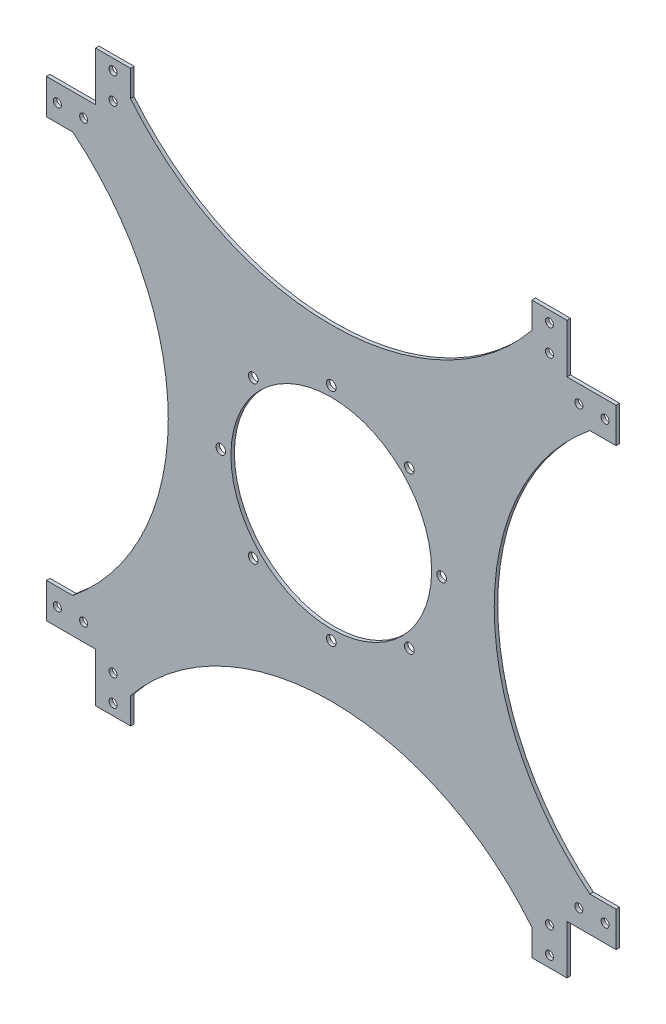
SolidWorks part; units mm, degrees
ref_plane "Front Plane" through (0, 0, 0) normal (0, 0, 1) x (1, 0, 0)
ref_plane "Top Plane" through (0, 0, 0) normal (0, 1, 0) x (1, 0, 0)
ref_plane "Right Plane" through (0, 0, 0) normal (1, 0, 0) x (0, 0, -1)
sketch "Sketch1" plane through (0, 0, 0) normal (0, 0, 1) x (1, 0, 0)
  line L0 (0, 0) -> (367.2182, 0) construction
  line L1 (0, 0) -> (0, -316.5866) construction
  line L2 (0, 0) -> (269, 269) construction
  line L3 (0, 0) -> (269, -269) construction
  line L4 (269, 269) -> (269, 325)
  line L5 (269, 269) -> (325, 269)
  line L6 (269, 325) -> (229, 325)
  line L7 (229, 325) -> (229, 295)
  line L8 (0, 0) -> (-269, 269) construction
  line L9 (0, 0) -> (-269, -269) construction
  line L10 (0, 0) -> (-199.7109, 0) construction
  line L11 (-269, 269) -> (-269, 325)
  line L12 (-269, 325) -> (-229, 325)
  line L13 (-229, 325) -> (-229, 295)
  line L14 (269, -269) -> (325, -269)
  line L15 (325, -269) -> (325, -229)
  line L16 (325, -229) -> (295, -229)
  line L17 (325, 269) -> (325, 229)
  line L18 (325, 229) -> (295, 229)
  line L19 (269, -269) -> (269, -325)
  line L20 (269, -325) -> (229, -325)
  line L21 (229, -325) -> (229, -295)
  line L22 (-229, -325) -> (-229, -295)
  line L23 (-269, -325) -> (-229, -325)
  line L24 (-269, -269) -> (-269, -325)
  line L25 (-269, -269) -> (-325, -269)
  line L26 (-325, -269) -> (-325, -229)
  line L27 (-325, -229) -> (-295, -229)
  line L28 (-325, 229) -> (-295, 229)
  line L29 (-325, 269) -> (-325, 229)
  line L30 (-269, 269) -> (-325, 269)
  circle A0 centre (0, 0) radius 114.5
  arc A1 (-229, 295) -> (229, 295) centre (0, 480.9677) ccw
  arc A2 (295, 229) -> (295, -229) centre (480.9677, 0) ccw
  arc A3 (-229, -295) -> (229, -295) centre (0, -480.9677) cw
  arc A4 (-295, 229) -> (-295, -229) centre (-480.9677, 0) cw
  dimension "D4" = 229
  dimension "D9" = 295
  dimension "D1" = 45
  dimension "D2" = 650
  dimension "D3" = 56
  dimension "D5" = 40
  dimension "D6" = 45
  dimension "D7" = 45
  dimension "D8" = 30
  dimension "D10" = 325
sheet metal parameters "Sheet-Metal1" thickness 4 parameters "D1"=1
base flange "Base-Flange1" sketch "Sketch1" thickness 4 reverse thickness direction yes parameters "D1"=1
sketch "Sketch2" plane through (0, 0, 4) normal (0, 0, 1) x (1, 0, 0)
  line L0 (269, 269) -> (269, 325) construction
  line L1 (269, 325) -> (229, 325) construction
  line L2 (325, 229) -> (325, 269) construction
  line L3 (325, 269) -> (269, 269) construction
  line L4 (0, 0) -> (260.8486, 0) construction
  line L5 (0, 0) -> (0, -250.4708) construction
  circle A0 centre (249, 312.5) radius 4.6
  circle A1 centre (249, 282.5) radius 4.6
  circle A2 centre (282.5, 249) radius 4.6
  circle A3 centre (312.5, 249) radius 4.6
  circle A4 centre (312.5, -249) radius 4.6
  circle A5 centre (282.5, -249) radius 4.6
  circle A6 centre (249, -282.5) radius 4.6
  circle A7 centre (249, -312.5) radius 4.6
  circle A8 centre (-249, -312.5) radius 4.6
  circle A9 centre (-249, -282.5) radius 4.6
  circle A10 centre (-282.5, -249) radius 4.6
  circle A11 centre (-312.5, -249) radius 4.6
  circle A12 centre (-312.5, 249) radius 4.6
  circle A13 centre (-282.5, 249) radius 4.6
  circle A14 centre (-249, 282.5) radius 4.6
  circle A15 centre (-249, 312.5) radius 4.6
  point P8 (269, 297)
  dimension "D2" = 9.2
  dimension "D1" = 20
  dimension "D3" = 12.5
  dimension "D4" = 30
  dimension "D5" = 30
  dimension "D6" = 12.5
  dimension "D7" = 20
extrude "Extrude1" cut sketch "Sketch2" against normal blind 4 normal cut yes
sketch "Sketch3" plane through (0, 0, 4) normal (0, 0, 1) x (1, 0, 0)
  line L0 (0, 0) -> (220.4396, 0) construction
  line L1 (0, 0) -> (0, -219.5819) construction
  line L2 (0, 0) -> (178.1909, 178.1909) construction
  circle A0 centre (0, 0) radius 126 construction
  circle A1 centre (0, 126) radius 5.5
  circle A2 centre (-126, 0) radius 5.5 construction
  circle A3 centre (0, -126) radius 5.5 construction
  circle A4 centre (126, 0) radius 5.5 construction
  dimension "D2" = 11
  dimension "D3" = 252
  dimension "D1" = 45
extrude "Extrude2" cut sketch "Sketch3" against normal blind 4 normal cut yes
pattern_circular "CirPattern1" count 8 over 360 about axis through (0, 0, 4) along (0, 0, 1) of "Extrude2"
flat pattern "Flat-Pattern1" [suppressed]
sketch "Bend-Lines1" plane through (0, 0, 0) normal (0, 1, 0) x (-1, 0, 0)
